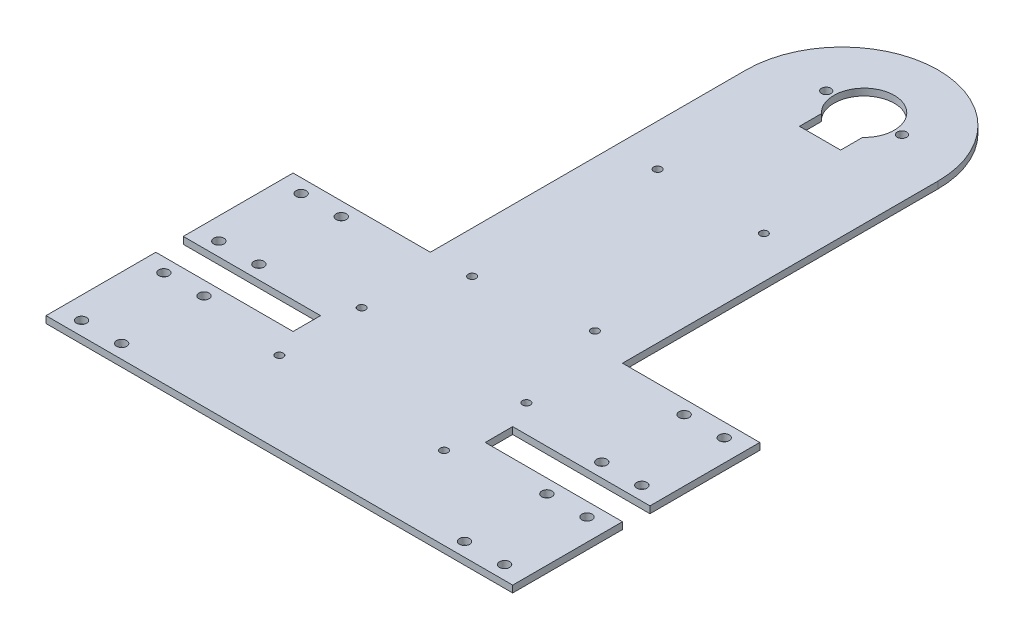
SolidWorks part; units mm, degrees
ref_plane "Front Plane" through (0, 0, 0) normal (0, 0, 1) x (1, 0, 0)
ref_plane "Top Plane" through (0, 0, 0) normal (0, 1, 0) x (1, 0, 0)
ref_plane "Right Plane" through (0, 0, 0) normal (1, 0, 0) x (0, 0, -1)
sketch "Sketch1" plane through (0, 0, 0) normal (0, 1, 0) x (1, 0, 0)
  line L0 (0, 152.4) -> (0, -152.4) construction
  line L2 (-44.45, 107.95) -> (-44.45, -152.4)
  line L3 (-44.45, -152.4) -> (44.45, -152.4)
  line L4 (44.45, 107.95) -> (44.45, -152.4)
  line L5 (-44.45, 152.4) -> (44.45, -152.4) construction
  line L6 (-44.45, -152.4) -> (44.45, 152.4) construction
  line L11 (-44.45, 152.4) -> (44.45, 152.4) construction
  line L12 (44.45, 152.4) -> (44.45, 107.95) construction
  line L13 (107.95, -152.4) -> (44.45, -152.4)
  line L14 (-107.95, -101.6) -> (-44.45, -101.6)
  line L15 (-107.95, -101.6) -> (-107.95, -152.4)
  line L16 (-107.95, -152.4) -> (-44.45, -152.4)
  line L17 (-44.45, -101.6) -> (-44.45, -152.4)
  line L18 (-107.95, -101.6) -> (-44.45, -152.4) construction
  line L19 (-107.95, -152.4) -> (-44.45, -101.6) construction
  line L20 (-107.95, -38.1) -> (-44.45, -38.1)
  line L21 (-107.95, -38.1) -> (-107.95, -88.9)
  line L22 (-107.95, -88.9) -> (-44.45, -88.9)
  line L23 (-44.45, -38.1) -> (-44.45, -88.9)
  line L24 (-107.95, -38.1) -> (-44.45, -88.9) construction
  line L25 (-107.95, -88.9) -> (-44.45, -38.1) construction
  line L26 (44.45, -101.6) -> (44.45, -152.4)
  line L27 (107.95, -101.6) -> (44.45, -101.6)
  line L28 (107.95, -101.6) -> (107.95, -152.4)
  line L29 (107.95, -88.9) -> (44.45, -88.9)
  line L30 (44.45, -38.1) -> (44.45, -88.9)
  line L31 (107.95, -38.1) -> (44.45, -38.1)
  line L32 (107.95, -38.1) -> (107.95, -88.9)
  line L37 (-44.45, 107.95) -> (-44.45, 152.4) construction
  arc A0 (-44.45, 107.95) -> (44.45, 107.95) centre (0, 107.95) cw
  point P0 (0, 0)
  point P12 (-76.2, -127)
  point P13 (-76.2, -63.5)
  dimension "D1" = 304.8
  dimension "D2" = 88.9
  dimension "D3" = 63.5
  dimension "D4" = 50.8
  dimension "D5" = 12.7
extrude "Boss-Extrude1" add sketch "Sketch1" along normal blind 3.175 contours L2 | L4 L2 L3 | L4 | L32 L31 L4 L29 | L28 L27 L4 L13 | L15 L16 L2 L14 | L21 L22 L2 L20 region at (0, 0, 4.6028) region at (-76.2, 0, 63.5) region at (76.2, 0, 63.5) region at (-76.2, 0, 127) region at (76.2, 0, 127)
sketch "Sketch2" plane through (0, 3.175, 0) normal (0, 1, 0) x (1, 0, 0)
  line L1 (-9.525, 107.8906) -> (-9.525, 97.7306)
  line L2 (-9.525, 97.7306) -> (9.525, 97.7306)
  line L3 (-44.45, 47.7291) -> (-26.9545, 47.7291) construction
  line L4 (-44.45, 107.95) -> (-44.45, -38.1) construction
  line L5 (26.9545, 46.5861) -> (44.45, 46.5861) construction
  line L6 (44.45, 107.95) -> (44.45, -38.1) construction
  line L7 (9.525, 97.7306) -> (9.525, 107.8906)
  line L12 (13.97, 118.11) -> (17.526, 118.11) construction
  line L13 (-13.97, 118.11) -> (-17.526, 118.11) construction
  line L14 (-44.45, -88.9) -> (-44.45, -101.6) construction
  circle A0 centre (-38.1, -76.2) radius 1.8097
  circle A1 centre (38.1, -76.2) radius 1.8097
  circle A2 centre (-38.1, -114.3) radius 1.8097
  circle A3 centre (38.1, -114.3) radius 1.8097
  circle A4 centre (-25.1447, 47.7291) radius 1.8098
  circle A5 centre (25.1447, 46.5861) radius 1.8098
  circle A6 centre (25.1447, -31.5697) radius 1.8098
  circle A7 centre (-25.1447, -38.1) radius 1.8098
  arc A8 (9.525, 107.8906) -> (-9.525, 107.8906) centre (0, 118.11) ccw
  circle A9 centre (-17.526, 118.11) radius 2.159
  circle A10 centre (17.526, 118.11) radius 2.159
  point P15 (-44.45, -95.25)
  point P36 (13.97, 118.11)
  point P41 (0, 97.7306)
  point P42 (-13.97, 118.11)
  dimension "D1" = 3.6195
  dimension "D2" = 38.1
  dimension "D3" = 76.2
  dimension "D8" = 50.2895
  dimension "D12" = 3.556
  dimension "D10" = 27.94
  dimension "D11" = 4.318
  dimension "D4" = 38.1
  dimension "D5" = 19.05
  dimension "D6" = 78.1558
  dimension "D7" = 85.8291
  dimension "D9" = 1.143
  dimension "D13" = 10.16
  dimension "D14" = 19.05
  dimension "D15" = 10.16
extrude "Cut-Extrude1" cut sketch "Sketch2" against normal through all contours A2 | A3 | A1 | A0 | A7 | A6 | A5 | A4 | L2 L7 A8 L1 | A9 | A10 region at (-38.1, 3.175, 76.2) region at (38.1, 3.175, 76.2) region at (-38.1, 3.175, 114.3) region at (38.1, 3.175, 114.3)
sketch "Sketch3" plane through (0, 3.175, 0) normal (0, 1, 0) x (1, 0, 0)
  line L0 (-97.8535, -44.45) -> (-107.95, -44.45) construction
  line L1 (-107.95, -38.1) -> (-107.95, -88.9) construction
  line L2 (-97.8535, -88.9) -> (-97.8535, -84.8995) construction
  line L4 (-107.95, -88.9) -> (-44.45, -88.9) construction
  line L6 (-44.45, -95.25) -> (-107.95, -95.25) construction
  line L7 (-44.45, -88.9) -> (-44.45, -101.6) construction
  line L8 (-97.8535, -107.95) -> (-97.8535, -100.9984) construction
  line L9 (-97.8535, -146.05) -> (-97.8535, -149.86) construction
  line L10 (-97.8535, -146.05) -> (-107.95, -146.05) construction
  line L11 (0, 0) -> (0, -152.4) construction
  line L12 (-107.95, -152.4) -> (107.95, -152.4) construction
  line L13 (97.8535, -146.05) -> (107.95, -146.05) construction
  line L14 (97.8535, -146.05) -> (97.8535, -149.86) construction
  line L15 (97.8535, -107.95) -> (97.8535, -100.9984) construction
  line L16 (44.45, -95.25) -> (107.95, -95.25) construction
  line L17 (97.8535, -82.55) -> (97.8535, -89.5016) construction
  line L18 (97.8535, -44.45) -> (97.8535, -40.64) construction
  line L19 (97.8535, -44.45) -> (107.95, -44.45) construction
  line L20 (-107.95, -38.1) -> (-44.45, -38.1) construction
  line L21 (-97.8535, -42.1005) -> (-97.8535, -38.1) construction
  circle A0 centre (-97.8535, -44.45) radius 2.3495
  circle A1 centre (-79.3115, -44.45) radius 2.3495
  circle A2 centre (-97.8535, -82.55) radius 2.3495
  circle A3 centre (-79.3115, -82.55) radius 2.3495
  circle A4 centre (-79.3115, -107.95) radius 2.3495
  circle A5 centre (-97.8535, -107.95) radius 2.3495
  circle A6 centre (-79.3115, -146.05) radius 2.3495
  circle A7 centre (-97.8535, -146.05) radius 2.3495
  circle A8 centre (97.8535, -146.05) radius 2.3495
  circle A9 centre (79.3115, -146.05) radius 2.3495
  circle A10 centre (97.8535, -107.95) radius 2.3495
  circle A11 centre (79.3115, -107.95) radius 2.3495
  circle A12 centre (79.3115, -82.55) radius 2.3495
  circle A13 centre (97.8535, -82.55) radius 2.3495
  circle A14 centre (79.3115, -44.45) radius 2.3495
  circle A15 centre (97.8535, -44.45) radius 2.3495
  point P13 (0, 0)
  point P65 (-97.8535, -84.4884)
  dimension "D1" = 4.699
  dimension "D3" = 18.542
  dimension "D2" = 10.0965
  dimension "D4" = 4.0005
extrude "Cut-Extrude2" cut sketch "Sketch3" against normal through all
